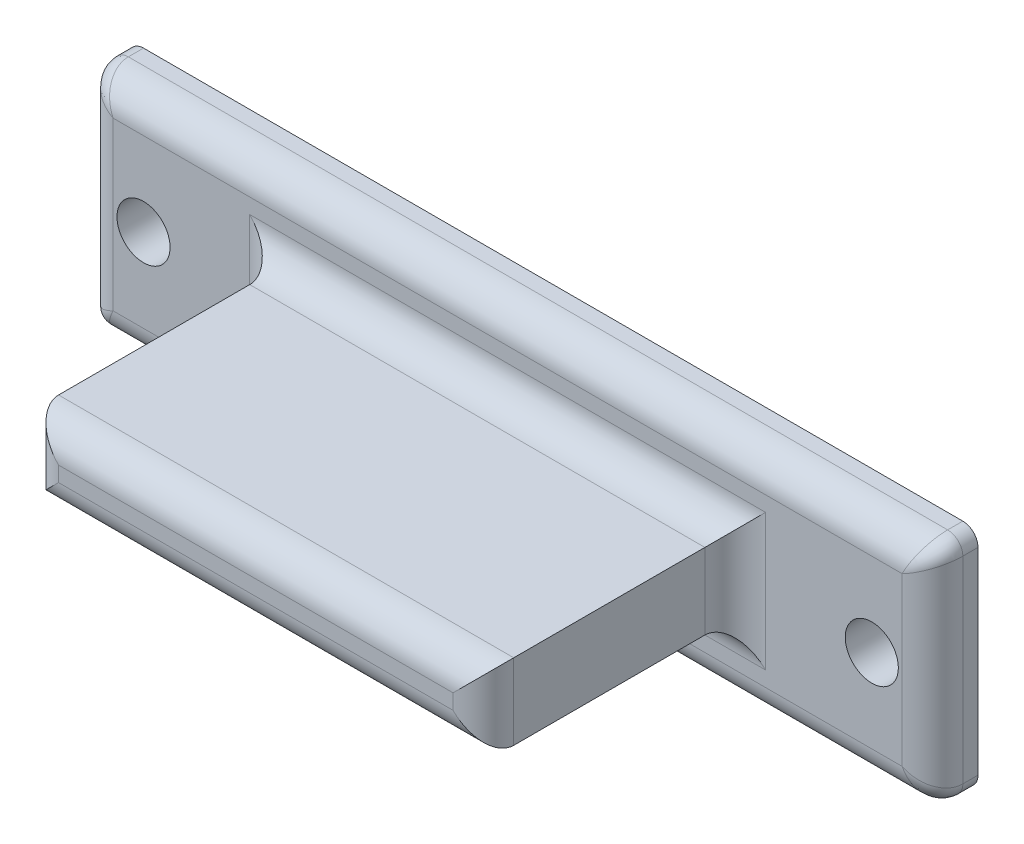
SolidWorks part; units mm, degrees
ref_plane "Front Plane" through (0, 0, 0) normal (0, 0, 1) x (1, 0, 0)
ref_plane "Top Plane" through (0, 0, 0) normal (0, 1, 0) x (1, 0, 0)
ref_plane "Right Plane" through (0, 0, 0) normal (1, 0, 0) x (0, 0, -1)
sketch "Sketch1" plane through (0, 0, 0) normal (0, 0, 1) x (1, 0, 0)
  line L0 (-31.4046, 0) -> (31.4046, 0) construction
  line L1 (-27, 7.5) -> (27, 7.5)
  line L2 (-28, 6.5) -> (-28, -6.5)
  line L3 (-27, -7.5) -> (27, -7.5)
  line L4 (28, 6.5) -> (28, -6.5)
  line L5 (-28, 7.5) -> (28, -7.5) construction
  line L6 (-28, -7.5) -> (28, 7.5) construction
  line L7 (0, 9.4204) -> (0, -9.4204) construction
  circle A0 centre (-24, 0) radius 1.75
  circle A1 centre (24, 0) radius 1.75
  arc A2 (27, -7.5) -> (28, -6.5) centre (27, -6.5) ccw
  arc A3 (28, 6.5) -> (27, 7.5) centre (27, 6.5) ccw
  arc A4 (-28, -6.5) -> (-27, -7.5) centre (-27, -6.5) ccw
  arc A5 (-28, 6.5) -> (-27, 7.5) centre (-27, 6.5) cw
  point P0 (0, 0)
  point P10 (0, 0)
  point P11 (0, 0)
  dimension "D3" = 24
  dimension "D4" = 3.5
  dimension "D5" = 1
  dimension "D1" = 56
  dimension "D2" = 15
extrude "Boss-Extrude1" add sketch "Sketch1" along normal blind 3
sketch "Sketch2" plane through (0, 0, 3) normal (0, 0, 1) x (1, 0, 0)
  line L7 (-15, 2.5) -> (15, 2.5)
  line L8 (-15, 2.5) -> (-15, -2.5)
  line L9 (-15, -2.5) -> (15, -2.5)
  line L10 (15, 2.5) -> (15, -2.5)
  line L11 (-15, 2.5) -> (15, -2.5) construction
  line L12 (-15, -2.5) -> (15, 2.5) construction
  point P11 (0, 0)
  dimension "D1" = 30
  dimension "D2" = 5
extrude "Boss-Extrude2" add sketch "Sketch2" along normal blind 16.6
fillet "Fillet2" radius 2 4 edges at (0, -2.5, 19.6) (-15, 0, 19.6) (0, 2.5, 19.6) (15, 0, 19.6)
fillet "Fillet3" radius 2 12 edges at (-15, 0, 3) (0, 2.5, 3) (15, 0, 3) (0, -2.5, 3) (27.7071, -7.2071, 3) (28, 0, 3) (27.7071, 7.2071, 3) (0, -7.5, 3) (-27.7071, -7.2071, 3) (-28, 0, 3) (-27.7071, 7.2071, 3) (0, 7.5, 3)
